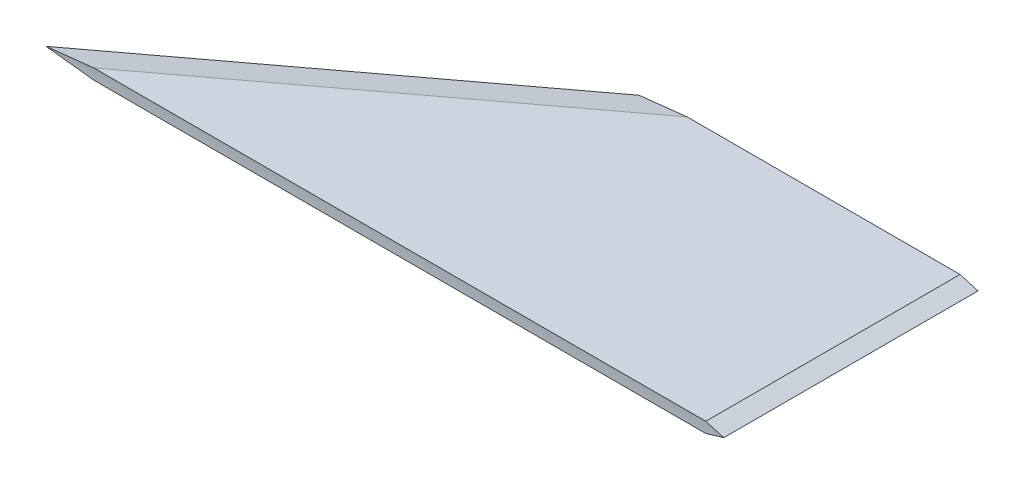
SolidWorks part; units mm, degrees
ref_plane "Front Plane" through (0, 0, 0) normal (0, 0, 1) x (1, 0, 0)
ref_plane "Top Plane" through (0, 0, 0) normal (0, 1, 0) x (1, 0, 0)
ref_plane "Right Plane" through (0, 0, 0) normal (1, 0, 0) x (0, 0, -1)
sketch "Sketch1" plane through (0, 0, 0) normal (0, 1, 0) x (1, 0, 0)
  line L0 (-101.6, 0) -> (101.6, 0)
  line L1 (-101.6, 0) -> (0, 76.2)
  line L2 (0, 76.2) -> (101.6, 76.2)
  line L3 (101.6, 76.2) -> (101.6, 0)
  point P4 (0, 0)
  dimension "D1" = 203.2
  dimension "D2" = 101.6
  dimension "D3" = 101.6
  dimension "D4" = 76.2
extrude "Boss-Extrude1" add sketch "Sketch1" along normal mid plane 3.175
sketch "Sketch2" plane through (0, 0, 0) normal (1, 0, 0) x (0, 0, -1)
  line L0 (0, 0) -> (-39.624, 0)
  line L1 (0, 1.5875) -> (-0.0318, 1.5875)
  line L2 (0, -1.5875) -> (-0.008, -0.7937)
  line L3 (0, 1.5875) -> (0, -1.5875)
  line L4 (0, -1.5875) -> (-0.0318, -1.5875)
  circle A0 centre (-39.624, 0) radius 39.624
  point P9 (0, 0)
  dimension "D1" = 79.248
extrude "Boss-Extrude2" add sketch "Sketch2" along normal mid plane 203.2 contours A0 L4 L2 | A0 L2 L3 | A0 L3 L1 region at (0, 1.1907, 0.0095) region at (0, -0.8731, 0.0025) region at (0, -1.335, 0.0127)
ref_plane "Plane2" through (0, 1.525, 0) normal (0, 1, 0) x (1, 0, 0)
ref_plane "Plane3" through (36.576, 0, -27.432) normal (0.8, 0, -0.6) x (0, -1, 0)
sketch "Sketch8" plane through (36.576, 0, -27.432) normal (0.8, 0, -0.6) x (0, -1, 0)
  line L0 (-1.5875, 60.96) -> (0, 60.96)
  line L1 (0, 60.96) -> (-1.5875, 52.2974)
  line L2 (-1.5875, 0) -> (-1.5875, 60.96) construction
  line L3 (0, 60.96) -> (1.5875, 52.255)
  line L4 (1.5875, 0) -> (1.5875, 60.96) construction
  line L5 (-1.5875, 52.2974) -> (-1.5875, 60.96)
  line L6 (1.5875, 60.96) -> (0, 60.96)
  line L7 (1.5875, 60.96) -> (1.5875, 52.255)
  dimension "D1" = 20.72
extrude "Cut-Extrude1" cut sketch "Sketch8" against normal mid plane 306 contours L5 L1 L0 | L7 L6 L3 region at (1.741, -1.0583, -73.8787) region at (1.7325, 1.0583, -73.89)
sketch "Sketch9" plane through (0, 0, -76.2) normal (0, 0, -1) x (-1, 0, 0)
  line L0 (-101.6, 0) -> (-96.2269, 1.5875)
  line L1 (-101.6, 1.5875) -> (-101.6, -1.5875) construction
  line L2 (-101.6, 1.5875) -> (-14.4376, 1.5875) construction
  line L3 (-101.6, 0) -> (-96.2269, -1.5875)
  line L4 (-101.6, -1.5875) -> (-14.5084, -1.5875) construction
  line L5 (-96.2269, -1.5875) -> (-101.6, -1.5875)
  line L6 (-101.6, -1.5875) -> (-101.6, 1.5875)
  line L7 (-101.6, 1.5875) -> (-96.2269, 1.5875)
  line M3 (-101.6, -1.5875) -> (-14.5084, -1.5875)
  line M6 (-14.4376, 1.5875) -> (-101.6, 1.5875)
  line M7 (-101.6, 1.5875) -> (-101.6, -1.5875)
  dimension "D1" = 32.92
extrude "Cut-Extrude2" cut sketch "Sketch9" against normal blind 136 contours L0 M7 M6 | L3 M7 M3 region at (99.809, 1.0583, -76.2) region at (99.809, -1.0583, -76.2)
